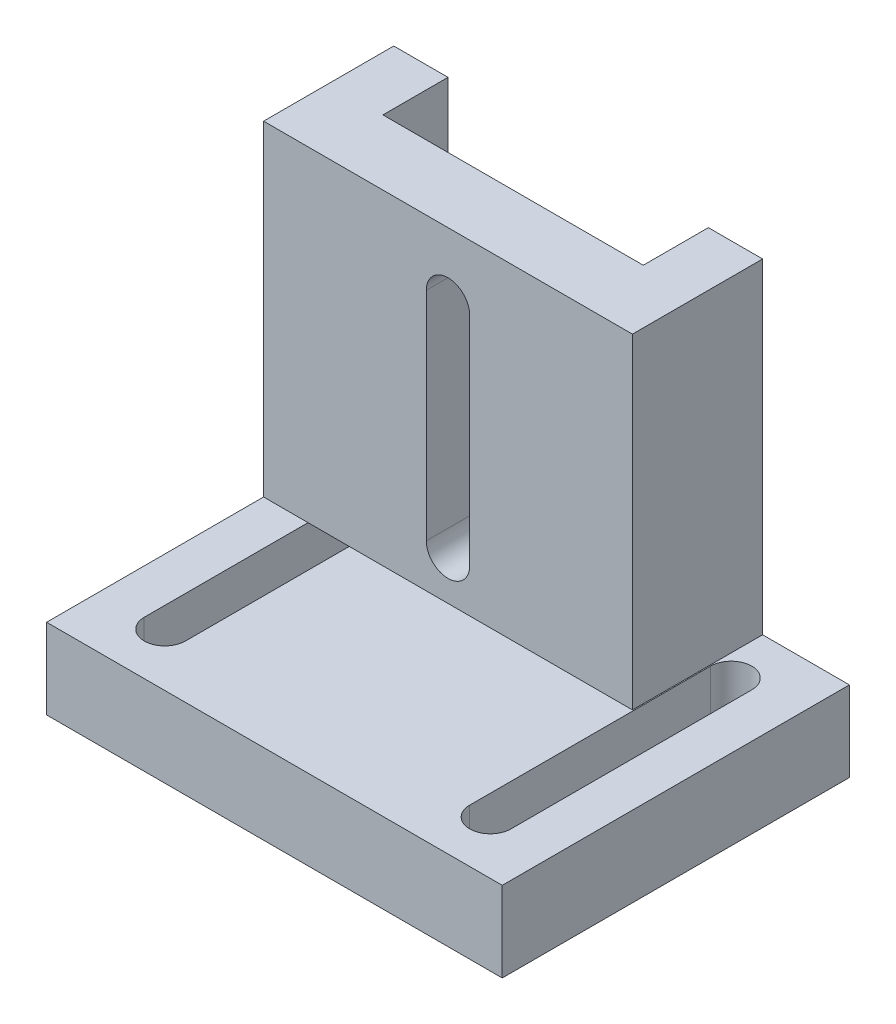
SolidWorks part; units mm, degrees
ref_plane "Front Plane" through (0, 0, 0) normal (0, 0, 1) x (1, 0, 0)
ref_plane "Top Plane" through (0, 0, 0) normal (0, 1, 0) x (1, 0, 0)
ref_plane "Right Plane" through (0, 0, 0) normal (1, 0, 0) x (0, 0, -1)
ref_axis "X-Axis" through (-88.99, 0, 0) along (1, 0, 0)
ref_axis "Y-Axis" through (0, 55, 0) along (0, -1, 0)
ref_axis "Z-Axis" through (0, 0, -88.99) along (0, 0, 1)
sketch "Sketch1" plane through (0, 0, 0) normal (0, 1, 0) x (1, 0, 0)
  line L1 (-5, 8) -> (5, 8)
  line L2 (-5, 8) -> (-5, -8)
  line L3 (-5, -8) -> (5, -8)
  line L4 (5, 8) -> (5, -8)
  line L5 (-5, 8) -> (5, -8) construction
  line L6 (-5, -8) -> (5, 8) construction
  point P0 (0, 0)
  dimension "D1" = 16
  dimension "D2" = 10
extrude "Boss-Extrude1" add sketch "Sketch1" along normal blind 3.7
sketch "Sketch2" plane through (0, 0, 0) normal (0, -1, 0) x (1, 0, 0)
  line L1 (-4.1, -7.15) -> (4.1, -7.15)
  line L2 (-4.1, -7.15) -> (-4.1, 7.15)
  line L3 (-4.1, 7.15) -> (4.1, 7.15)
  line L4 (4.1, -7.15) -> (4.1, 7.15)
  line L5 (-4.1, -7.15) -> (4.1, 7.15) construction
  line L6 (-4.1, 7.15) -> (4.1, -7.15) construction
  point P0 (0, 0)
  dimension "D1" = 14.3
  dimension "D2" = 8.2
sketch "Sketch4" plane through (0, 3.7, 0) normal (0, 1, 0) x (1, 0, 0)
  line L1 (-3.25, -5) -> (3.25, -5)
  line L2 (-3.25, -5) -> (-3.25, 5)
  line L3 (-3.25, 5) -> (3.25, 5)
  line L4 (3.25, -5) -> (3.25, 5)
  line L5 (-3.25, -5) -> (3.25, 5) construction
  line L6 (-3.25, 5) -> (3.25, -5) construction
  point P0 (0, 0)
  dimension "D1" = 6.5
  dimension "D2" = 10
sketch "Sketch5" plane through (0, 0, 0) normal (0, -1, 0) x (1, 0, 0)
  line L1 (-10.5, 8) -> (-5, 8)
  line L2 (-10.5, 8) -> (-10.5, -8)
  line L3 (-10.5, -8) -> (-5, -8)
  line L4 (-5, 8) -> (-5, -8)
  dimension "D1" = 5.5
extrude "Boss-Extrude2" add sketch "Sketch5" against normal blind 3.7
sketch "Sketch6" plane through (0, 3.7, 0) normal (0, 1, 0) x (1, 0, 0)
  line L0 (-7.5, 6.5) -> (-7.5, -6.5) construction
  line L3 (-7.5, 5.55) -> (-7.5, -5.55) construction
  line L4 (-6.55, 5.55) -> (-6.55, -5.55)
  line L5 (-8.45, 5.55) -> (-8.45, -5.55)
  line L6 (-7.5, 6.5) -> (-7.5, 8) construction
  line L7 (-7.5, -6.5) -> (-7.5, -8) construction
  line L8 (-10.5, -8) -> (-10.5, 8) construction
  arc A0 (-6.55, 5.55) -> (-8.45, 5.55) centre (-7.5, 5.55) ccw
  arc A1 (-8.45, -5.55) -> (-6.55, -5.55) centre (-7.5, -5.55) ccw
  point P8 (-7.5, 0)
  dimension "D2" = 0.95
  dimension "D1" = 1.5
  dimension "D3" = 3
extrude "Cut-Extrude4" cut sketch "Sketch6" against normal through all
mirror "Mirror1" about plane through (0, 0, 0) normal (1, 0, 0) of "Cut-Extrude4", "Boss-Extrude2"
sketch "Sketch7" plane through (0, 0, 0) normal (0, 0, 1) x (1, 0, 0)
  line L11 (-10.5, 3.7) -> (6.5, 3.7)
  line L18 (-10.5, 3.7) -> (-10.5, 18.7)
  line L19 (-10.5, 18.7) -> (6.5, 18.7)
  line L20 (6.5, 18.7) -> (6.5, 3.7)
  line L21 (-2, 3.7) -> (-2, 18.7) construction
  line L24 (-3, 15.7) -> (-3, 5.7)
  line L26 (-1, 15.7) -> (-1, 5.7)
  arc A1 (-3, 15.7) -> (-1, 15.7) centre (-2, 15.7) cw
  arc A5 (-3, 5.7) -> (-1, 5.7) centre (-2, 5.7) ccw
  point P12 (0, 0)
  point P13 (-2, 16.1571)
  point P14 (0, 0)
  point P15 (0, 0)
  point P16 (0, 0)
  dimension "D1" = 2
  dimension "D2" = 2
  dimension "D3" = 2
  dimension "D4" = 10
  dimension "D5" = 3
  dimension "D6" = 7.5
  dimension "D7" = 7.5
extrude "Boss-Extrude3" add sketch "Sketch7" against normal blind 3 from offset 2 separate body offset against normal yes
sketch "Sketch8" plane through (0, 0, -5) normal (0, 0, -1) x (-1, 0, 0)
  line L0 (-10.5, 3.7) -> (10.5, 3.7) construction
  line L1 (-6.5, 18.7) -> (-4, 18.7)
  line L2 (-6.5, 18.7) -> (-6.5, 3.7)
  line L3 (-6.5, 3.7) -> (-4, 3.7)
  line L4 (-4, 18.7) -> (-4, 3.7)
  line L6 (10.5, 18.7) -> (8, 18.7)
  line L7 (10.5, 18.7) -> (10.5, 3.7)
  line L8 (10.5, 3.7) -> (8, 3.7)
  line L9 (8, 18.7) -> (8, 3.7)
  line L11 (-6.5, 18.7) -> (10.5, 18.7) construction
  line L12 (1, 5.7) -> (1, 15.7) construction
  line L13 (3, 15.7) -> (3, 5.7) construction
  point P12 (-10.5, 13.7)
  point P13 (0, 0)
  point P14 (0, 0)
  point P15 (10.5, 20.7)
  point P16 (-10.5, 20.7)
  point P17 (0, 0)
  point P21 (-10.5, 20.7)
  point P24 (0, 0)
  dimension "D1" = 2.5
  dimension "D2" = 2.5
  dimension "D3" = 5
  dimension "D4" = 5
extrude "Boss-Extrude5" add sketch "Sketch8" along normal blind 3
equation "\"D2@Sketch6\"=1.90mm/2"
